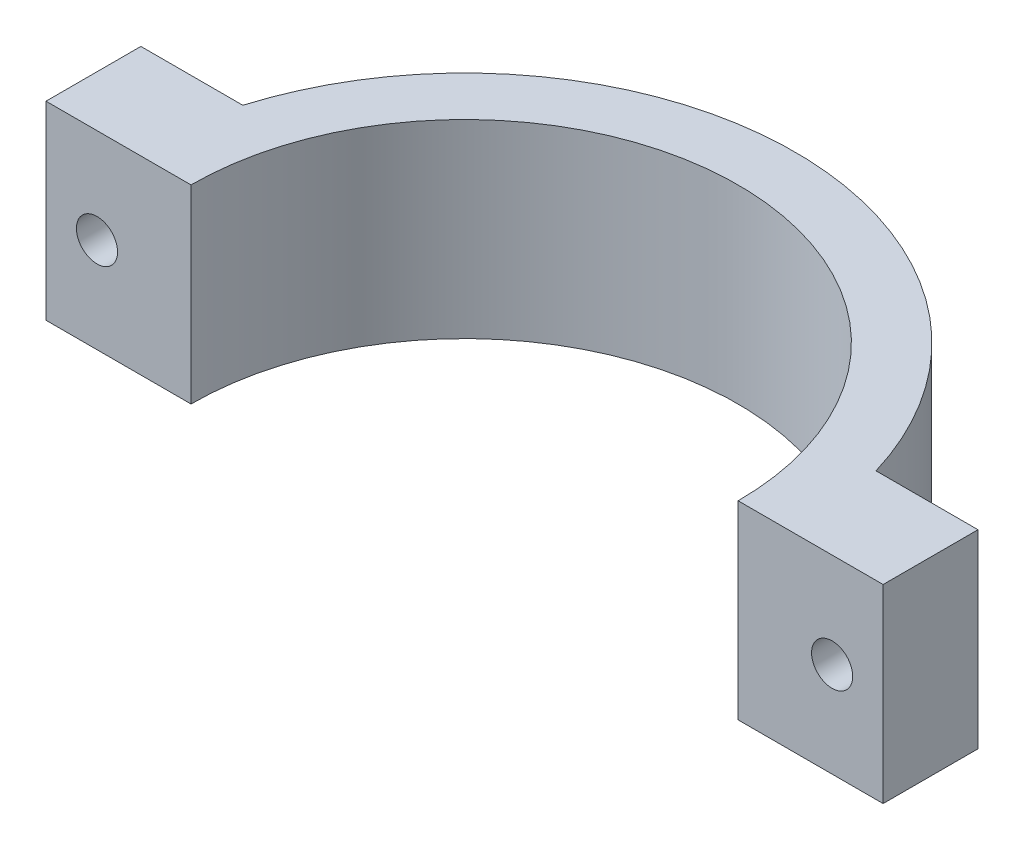
SolidWorks part; units mm, degrees
ref_plane "Front Plane" through (0, 0, 0) normal (0, 0, 1) x (1, 0, 0)
ref_plane "Top Plane" through (0, 0, 0) normal (0, 1, 0) x (1, 0, 0)
ref_plane "Right Plane" through (0, 0, 0) normal (1, 0, 0) x (0, 0, -1)
sketch "Sketch1" plane through (0, 0, 0) normal (0, 1, 0) x (1, 0, 0)
  line L3 (0, 0) -> (0, 43.25) construction
  line L14 (-66.175, 0) -> (-66.175, 15)
  line L16 (43.25, 0) -> (66.175, 0)
  line L17 (66.175, 0) -> (66.175, 15)
  line L18 (-66.175, 0) -> (-43.25, 0)
  line L19 (-66.175, 15) -> (-50.0506, 15)
  line L20 (50.0506, 15) -> (66.175, 15)
  circle A0 centre (0, 0) radius 43.25 construction
  arc A1 (-43.25, 0) -> (43.25, 0) centre (0, 0) cw
  arc A2 (-50.0506, 15) -> (50.0506, 15) centre (0, 0) cw
  dimension "D1" = 86.5
  dimension "D2" = 52.25
  dimension "D3" = 15
  dimension "D4" = 132.35
extrude "Boss-Extrude1" add sketch "Sketch1" along normal mid plane 30
sketch "Sketch2" plane through (0, 0, -15) normal (0, 0, -1) x (-1, 0, 0)
  line L0 (58.1128, -15) -> (58.1128, 15) construction
  line L1 (50.0506, -15) -> (66.175, -15) construction
  line L2 (50.0506, 15) -> (66.175, 15) construction
  line L3 (0, 0) -> (0, 15) construction
  line L4 (50.0506, 15) -> (-50.0506, 15) construction
  circle A1 centre (58.1128, 0) radius 3.25
  circle A2 centre (-58.1128, 0) radius 3.25
  dimension "D1" = 6.5
extrude "Cut-Extrude1" cut sketch "Sketch2" against normal through all
sketch "Sketch4" plane through (0, 15, 0) normal (0, 1, 0) x (1, 0, 0)
  line L0 (-50.0506, 15) -> (-50.0506, 35)
  line L1 (-50.0506, 35) -> (-38.7951, 35)
  arc A0 (50.0506, 15) -> (-50.0506, 15) centre (0, 0) ccw construction
  arc A1 (-38.7951, 35) -> (-50.0506, 15) centre (0, 0) ccw
  point P8 (-45.5345, 25.6256)
  dimension "D1" = 20
extrude "Boss-Extrude2" [suppressed] add sketch "Sketch4" against normal up to surface (30 mm away) up to face at (0, -15, -17.5625)
ref_plane "Plane1" [suppressed] through (0, 0, 0) normal (-1, 0, 0) x (0, 0, 1)
mirror "Mirror1" [suppressed] about plane through (0, 0, 0) normal (-1, 0, 0)
